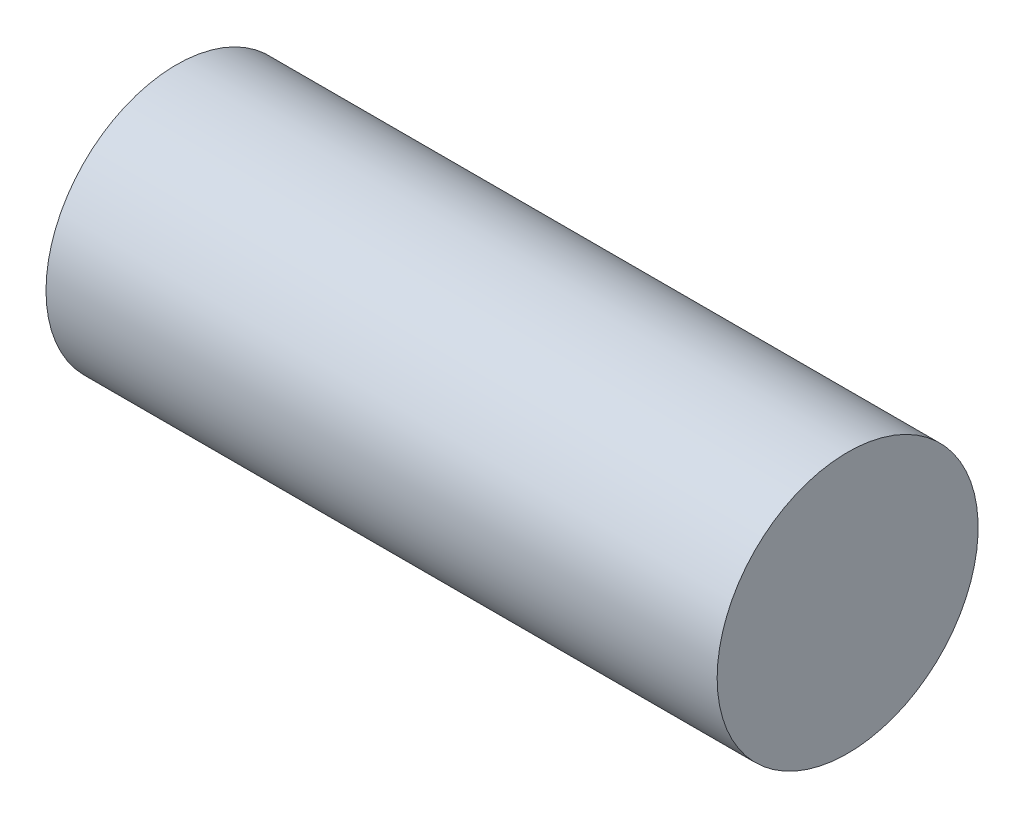
SolidWorks part; units mm, degrees
material "Nylon 101"
ref_plane "Front Plane" through (0, 0, 0) normal (0, 0, 1) x (1, 0, 0)
ref_plane "Top Plane" through (0, 0, 0) normal (0, 1, 0) x (1, 0, 0)
ref_plane "Right Plane" through (0, 0, 0) normal (1, 0, 0) x (0, 0, -1)
sketch "Sketch1" plane through (0, 0, 0) normal (1, 0, 0) x (0, 0, -1)
  circle A0 centre (0, 0) radius 35
  dimension "D1" = 70
extrude "Boss-Extrude1" add sketch "Sketch1" along normal mid plane 180
